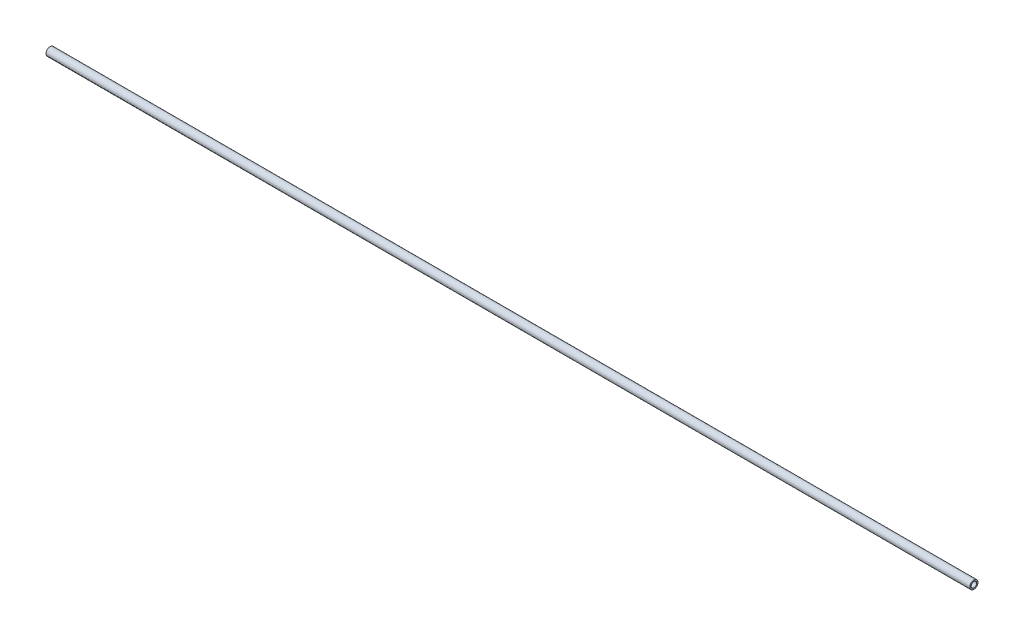
SolidWorks part; units mm, degrees
material "windcatcher"
ref_plane "Front Plane" through (0, 0, 0) normal (0, 0, 1) x (1, 0, 0)
ref_plane "Top Plane" through (0, 0, 0) normal (0, 1, 0) x (1, 0, 0)
ref_plane "Right Plane" through (0, 0, 0) normal (1, 0, 0) x (0, 0, -1)
sketch "Sketch1" plane through (0, 0, 0) normal (1, 0, 0) x (0, 0, -1)
  circle A0 centre (0, 0) radius 3
  circle A1 centre (0, 0) radius 2
  dimension "D1" = 6
  dimension "D2" = 4
extrude "Boss-Extrude1" add sketch "Sketch1" along normal mid plane 675
